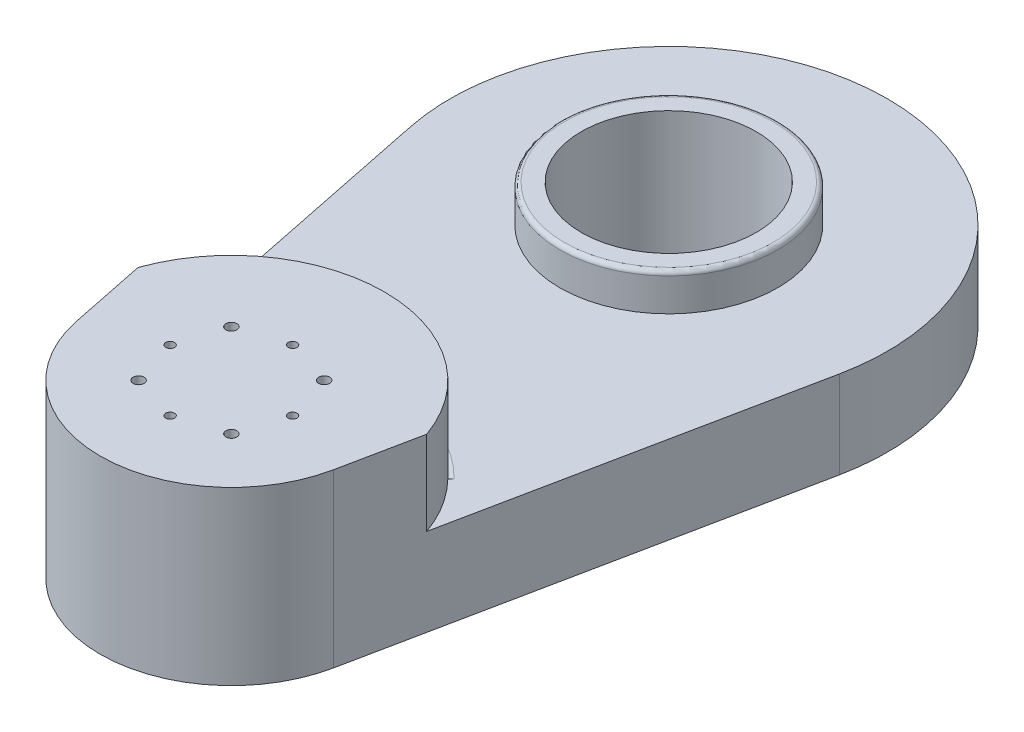
SolidWorks part; units mm, degrees
ref_plane "前视基准面" through (0, 0, 0) normal (0, 0, 1) x (1, 0, 0)
ref_plane "上视基准面" through (0, 0, 0) normal (0, 1, 0) x (1, 0, 0)
ref_plane "右视基准面" through (0, 0, 0) normal (1, 0, 0) x (0, 0, -1)
other "Configuration Table"
sketch "草图1" plane through (0, 0, 0) normal (0, 1, 0) x (1, 0, 0)
  line L0 (-57.8337, 33.3262) -> (-28.3029, -111.3445)
  line L6 (52.2485, 5.9643) -> (26.0098, -122.5784)
  circle A0 centre (0, 0) radius 50
  circle A1 centre (0, -100) radius 30
  dimension "D2" = 100
  dimension "D3" = 60
  dimension "D1" = 100
  dimension "D4" = 0
extrude "凸台-拉伸1" add sketch "草图1" along normal blind 20 contours A0 | A0 | A1 A0 | A1 region at (0, 0, 59.4922) region at (0, 0, 0) region at (0, 0, 100)
sketch "草图2" plane through (0, 20, 0) normal (0, 1, 0) x (1, 0, 0)
  circle A0 centre (0, 0) radius 24.9
  dimension "D1" = 49.8
extrude "凸台-拉伸2" add sketch "草图2" along normal blind 8.5
fillet "圆角1" radius 1 1 edges at (0, 28.5, 24.9)
sketch "草图3" plane through (0, 20, 0) normal (0, 1, 0) x (1, 0, 0)
  circle A0 centre (0, -100) radius 35
  dimension "D1" = 70
extrude "切除-拉伸1" cut sketch "草图3" against normal blind 5
sketch "草图4" plane through (0, 15, 0) normal (0, 1, 0) x (1, 0, 0)
  line L0 (-25, -75.5051) -> (0, -100)
  line L1 (0, -100) -> (25, -75.5051)
  line L6 (-32.9994, -88.3365) -> (-29.3939, -106)
  line L7 (-32.9994, -88.3365) -> (-29.3939, -106)
  line L8 (29.3939, -106) -> (32.9994, -88.3365)
  line L9 (29.3939, -106) -> (32.9994, -88.3365)
  circle A0 centre (0, -100) radius 19
  arc A3 (-29.3939, -106) -> (29.3939, -106) centre (0, -100) ccw
  arc A4 (32.9994, -88.3365) -> (-32.9994, -88.3365) centre (0, -100) ccw
  arc A5 (-29.3939, -106) -> (29.3939, -106) centre (0, -100) ccw
  arc A6 (32.9994, -88.3365) -> (-32.9994, -88.3365) centre (0, -100) ccw
  line M5 (-32.9994, -88.3365) -> (-29.3939, -106)
  arc M6 (-29.3939, -106) -> (29.3939, -106) centre (0, -100) ccw
  line M7 (29.3939, -106) -> (32.9994, -88.3365)
  arc M8 (32.9994, -88.3365) -> (-32.9994, -88.3365) centre (0, -100) ccw
  dimension "D1" = 38
  dimension "D3" = 25
  dimension "D4" = 25
  dimension "D2" = 0
extrude "凸台-拉伸4" add sketch "草图4" along normal blind 24.25 contours A0 L0 L1 M8 M5 M6 M7 region at (-19.8847, 15, 81.7153)
fillet "圆角2" radius 5 2 edges at (13.5714, 27.125, 86.7028) (-13.5714, 27.125, 86.7028)
sketch "草图5" plane through (0, 15, 0) normal (0, 1, 0) x (1, 0, 0)
  line L2 (-25, -75.5051) -> (-16.7667, -83.572)
  line L3 (16.7667, -83.572) -> (25, -75.5051)
  line L4 (-25, -75.5051) -> (-16.7667, -83.572)
  line L5 (16.7667, -83.572) -> (25, -75.5051)
  arc A4 (-16.0439, -89.8219) -> (-16.7667, -83.572) centre (-20.266, -87.1435) ccw
  arc A5 (-16.0439, -89.8219) -> (16.0439, -89.8219) centre (0, -100) ccw
  arc A6 (16.7667, -83.572) -> (16.0439, -89.8219) centre (20.266, -87.1435) ccw
  arc A7 (25, -75.5051) -> (-25, -75.5051) centre (0, -100) ccw
  arc A8 (-16.0439, -89.8219) -> (-16.7667, -83.572) centre (-20.266, -87.1435) ccw
  arc A9 (-16.0439, -89.8219) -> (16.0439, -89.8219) centre (0, -100) ccw
  arc A10 (16.7667, -83.572) -> (16.0439, -89.8219) centre (20.266, -87.1435) ccw
  arc A11 (25, -75.5051) -> (-25, -75.5051) centre (0, -100) ccw
  dimension "D1" = 0
fillet "圆角3" radius 1 1 edges at (0, 20, 65)
extrude "切除-拉伸2" cut sketch "草图5" against normal through all
sketch "草图6" plane through (0, 39.25, 0) normal (0, 1, 0) x (1, 0, 0)
  line L4 (25, -75.5051) -> (16.7667, -83.572)
  line L5 (-16.7667, -83.572) -> (-25, -75.5051)
  line L6 (-32.9994, -88.3365) -> (-29.3939, -106)
  line L7 (-32.9994, -88.3365) -> (-29.3939, -106)
  line L8 (25, -75.5051) -> (16.7667, -83.572)
  line L9 (-16.7667, -83.572) -> (-25, -75.5051)
  line L12 (29.3939, -106) -> (32.9994, -88.3365)
  line L13 (29.3939, -106) -> (32.9994, -88.3365)
  circle A0 centre (0, -100) radius 35
  arc A6 (16.7667, -83.572) -> (16.0439, -89.8219) centre (20.266, -87.1435) ccw
  arc A7 (-16.0439, -89.8219) -> (16.0439, -89.8219) centre (0, -100) ccw
  arc A8 (-16.0439, -89.8219) -> (-16.7667, -83.572) centre (-20.266, -87.1435) ccw
  arc A9 (-25, -75.5051) -> (-32.9994, -88.3365) centre (0, -100) ccw
  arc A11 (-29.3939, -106) -> (29.3939, -106) centre (0, -100) ccw
  arc A12 (16.7667, -83.572) -> (16.0439, -89.8219) centre (20.266, -87.1435) ccw
  arc A13 (-16.0439, -89.8219) -> (16.0439, -89.8219) centre (0, -100) ccw
  arc A14 (-16.0439, -89.8219) -> (-16.7667, -83.572) centre (-20.266, -87.1435) ccw
  arc A15 (-25, -75.5051) -> (-32.9994, -88.3365) centre (0, -100) ccw
  arc A18 (-29.3939, -106) -> (29.3939, -106) centre (0, -100) ccw
  arc A19 (32.9994, -88.3365) -> (25, -75.5051) centre (0, -100) ccw
  arc A20 (32.9994, -88.3365) -> (25, -75.5051) centre (0, -100) ccw
  line M11 (25, -75.5051) -> (16.7667, -83.572)
  arc M12 (16.7667, -83.572) -> (16.0439, -89.8219) centre (20.266, -87.1435) ccw
  arc M13 (16.0439, -89.8219) -> (-16.0439, -89.8219) centre (0, -100) cw
  arc M14 (-16.0439, -89.8219) -> (-16.7667, -83.572) centre (-20.266, -87.1435) ccw
  line M15 (-16.7667, -83.572) -> (-25, -75.5051)
  arc M16 (-25, -75.5051) -> (-32.9994, -88.3365) centre (0, -100) ccw
  line M17 (-32.9994, -88.3365) -> (-29.3939, -106)
  arc M18 (-29.3939, -106) -> (29.3939, -106) centre (0, -100) ccw
  line M19 (29.3939, -106) -> (32.9994, -88.3365)
  arc M20 (32.9994, -88.3365) -> (25, -75.5051) centre (0, -100) ccw
  dimension "D1" = 0
extrude "凸台-拉伸6" add sketch "草图6" against normal blind 4 contours M20 M11 M12 M13 M14 M15 M16 M17 M18 M19 | A0 M11 M15 M14 M13 M12 region at (28.9746, 39.25, 81.9364) region at (0, 39.25, 90.5682)
sketch "草图7" plane through (0, 39.25, 0) normal (0, 1, 0) x (1, 0, 0)
  circle A0 centre (0, -86) radius 2.5
  circle A1 centre (-14, -100) radius 2.5
  arc A2 (-17.75, -100) -> (17.75, -100) centre (0, -100) ccw
  arc A3 (17.75, -100) -> (-17.75, -100) centre (0, -100) ccw
  circle A4 centre (0, -114) radius 2.5
  circle A5 centre (14, -100) radius 2.5
  circle A6 centre (0, -86) radius 1
  circle A7 centre (14, -100) radius 1
  circle A8 centre (0, -114) radius 1
  circle A9 centre (-14, -100) radius 1
  circle A10 centre (-10.6066, -89.3934) radius 1.25
  circle A11 centre (10.6066, -89.3934) radius 1.25
  circle A12 centre (10.6066, -110.6066) radius 1.25
  circle A13 centre (-10.6066, -110.6066) radius 1.25
  point P24 (0, 0)
extrude "切除-拉伸3" cut sketch "草图7" against normal through all contours A9 | A6 | A11 | A7 | A12 | A13 | A10 | A8 region at (0, 39.25, 86) region at (14, 39.25, 100) region at (-14, 39.25, 100) region at (10.6066, 39.25, 89.3934) region at (10.6066, 39.25, 110.6066) region at (-10.6066, 39.25, 110.6066)
sketch "草图8" plane through (0, 28.5, 0) normal (0, 1, 0) x (1, 0, 0)
  circle A0 centre (0, 0) radius 20
  dimension "D1" = 40
extrude "切除-拉伸4" cut sketch "草图8" against normal through all
